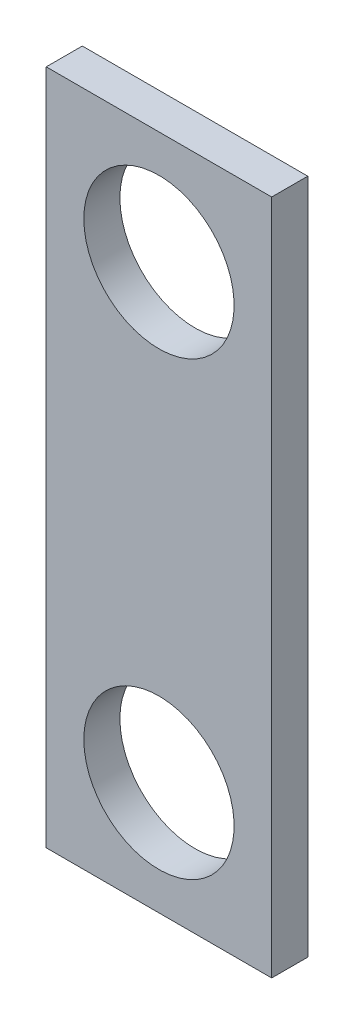
SolidWorks part; units mm, degrees
ref_plane "Front Plane" through (0, 0, 0) normal (0, 0, 1) x (1, 0, 0)
ref_plane "Top Plane" through (0, 0, 0) normal (0, 1, 0) x (1, 0, 0)
ref_plane "Right Plane" through (0, 0, 0) normal (1, 0, 0) x (0, 0, -1)
sketch "Sketch1" plane through (0, 0, 0) normal (0, 0, 1) x (1, 0, 0)
  line L0 (0, -180.975) -> (0, -219.075) construction
  line L1 (0, -200.025) -> (-9.525, -200.025) construction
  line L2 (-9.525, -228.6) -> (9.525, -228.6)
  line L3 (-9.525, -228.6) -> (-9.525, -171.45)
  line L4 (-9.525, -171.45) -> (9.525, -171.45)
  line L5 (9.525, -228.6) -> (9.525, -171.45)
  line L6 (-9.525, -228.6) -> (9.525, -171.45) construction
  line L7 (-9.525, -171.45) -> (9.525, -228.6) construction
  circle A0 centre (0, -180.975) radius 3.9687 construction
  circle A1 centre (0, -200.025) radius 3.175 construction
  circle A2 centre (0, -180.975) radius 6.35
  circle A3 centre (0, -219.075) radius 3.9687 construction
  circle A4 centre (0, -219.075) radius 6.35
  dimension "D1" = 7.9375
  dimension "D2" = 6.35
  dimension "D3" = 19.05
  dimension "D6" = 12.7
  dimension "D4" = 19.05
  dimension "D5" = 57.15
extrude "Boss-Extrude2" add sketch "Sketch1" along normal blind 3.048
